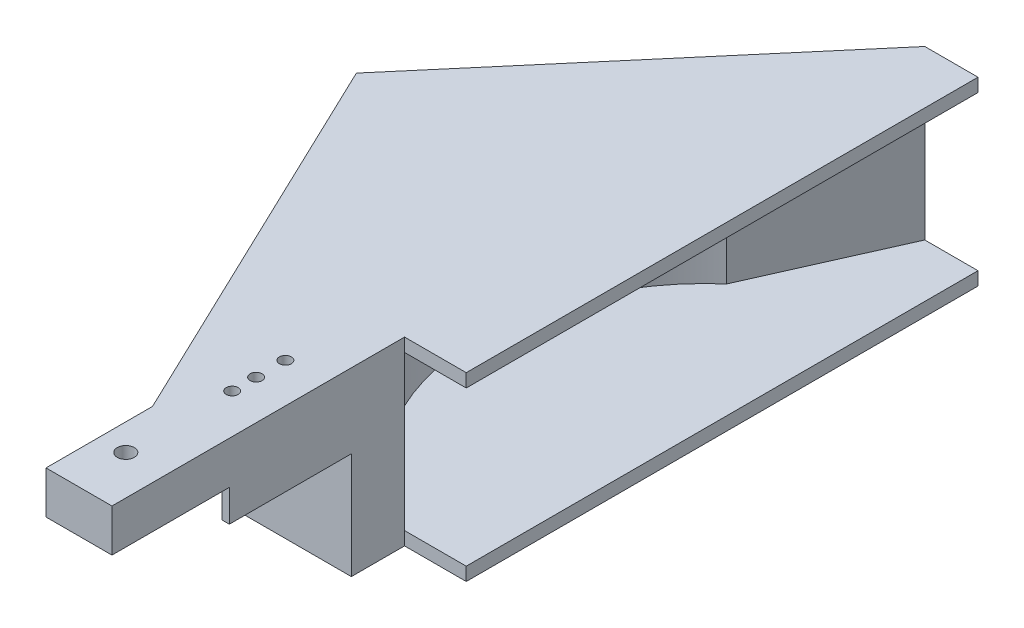
SolidWorks part; units mm, degrees
ref_plane "Front Plane" through (0, 0, 0) normal (0, 0, 1) x (1, 0, 0)
ref_plane "Top Plane" through (0, 0, 0) normal (0, 1, 0) x (1, 0, 0)
ref_plane "Right Plane" through (0, 0, 0) normal (1, 0, 0) x (0, 0, -1)
sketch "Sketch1" plane through (0, 0, 0) normal (0, 1, 0) x (1, 0, 0)
  line L0 (47.5, -78.4427) -> (47.5, -38.4427)
  line L1 (49.0919, 57.7552) -> (0, 0)
  line L2 (0, 0) -> (35.1, -73.4224)
  line L6 (35.1, -73.4224) -> (35.1, -93.4427)
  line L8 (37.5, -78.4427) -> (37.5, -93.4427) construction
  line L9 (37.5, -93.4427) -> (47.5, -93.4427)
  line L10 (47.5, -78.4427) -> (47.5, -93.4427)
  line L11 (35.1, -93.4427) -> (37.5, -93.4427)
  line L12 (35.1, -73.4224) -> (37.5, -78.4427) construction
  line L13 (49.0919, 57.7552) -> (37.628, 31.9779)
  arc A0 (37.628, 31.9779) -> (47.5, -38.4427) centre (65.622, 0) ccw
  point P6 (37.5, 31.9779)
  point P10 (47.5, 50)
  point P12 (49.0919, 57.7552)
  point P15 (51.2566, 50)
  point P16 (49.1521, 50)
  point P17 (50.3263, 51.8331)
  point P19 (0, 0)
  dimension "D1" = 85
  dimension "D10" = 114.085
  dimension "D2" = 50
  dimension "D3" = 40
  dimension "D4" = 47.5
  dimension "D5" = 10
  dimension "D8" = 15
  dimension "D9" = 12.4
extrude "Boss-Extrude1" add sketch "Sketch1" along normal blind 14
sketch "Sketch3" plane through (0, 0, 0) normal (0, -1, 0) x (1, 0, 0)
  line L6 (47.5, 93.4427) -> (47.5, 38.4427) construction
  line L7 (35.1, 93.4427) -> (47.5, 93.4427) construction
  line L8 (36.1851, 83.429) -> (36.1851, 109.2435) construction
  line L9 (33.255, 84.4031) -> (36.1851, 92.429)
  line L10 (35.3457, 53.1123) -> (33.255, 84.4031)
  line L11 (46.1351, 70.029) -> (44.8209, 53.0622)
  line L12 (46.1351, 88.029) -> (46.1351, 70.029)
  line L13 (44.8851, 92.429) -> (46.1351, 88.029)
  line L14 (36.1851, 92.429) -> (44.8851, 92.429)
  circle A6 centre (40.0851, 83.429) radius 6.75 construction
  circle A7 centre (40.0851, 83.429) radius 4.125
  circle A8 centre (40.0851, 63.429) radius 1.5 construction
  circle A9 centre (40.0851, 58.929) radius 1.5 construction
  circle A10 centre (40.0851, 53.429) radius 1.5 construction
  arc A11 (44.8209, 53.0622) -> (35.3457, 53.1123) centre (40.0851, 53.429) cw
  point P48 (33.3351, 83.429)
  dimension "D6" = 1.3649
  dimension "D7" = 2.6149
  dimension "D8" = 2.6791
  dimension "D12" = 1.0137
  dimension "D13" = 5.4137
  dimension "D1" = 3
  dimension "D3" = 8.25
  dimension "D4" = 13.5
  dimension "D5" = 4.75
  dimension "D2" = 40.0851
  dimension "D9" = 11.3149
  dimension "D10" = 12.1543
  dimension "D11" = 14.245
  dimension "D17" = 30.0137
  dimension "D18" = 34.5137
extrude "Cut-Extrude1" cut sketch "Sketch3" against normal blind 6
sketch "Sketch5" plane through (0, 6, 0) normal (0, -1, 0) x (1, 0, 0)
  circle A0 centre (40.0851, 63.429) radius 1.125
  circle A1 centre (40.0851, 58.929) radius 1.125
  circle A2 centre (40.0851, 53.429) radius 1.125
  circle A3 centre (40.0851, 63.429) radius 1.5 construction
  circle A4 centre (40.0851, 58.929) radius 1.5 construction
  circle A5 centre (40.0851, 53.429) radius 1.5 construction
  dimension "D1" = 2.25
extrude "Cut-Extrude2" cut sketch "Sketch5" against normal blind 15
sketch "Sketch15" plane through (0, 6, 0) normal (0, -1, 0) x (-1, 0, 0)
  line L1 (-32.171, -71.3827) -> (-57.8606, -71.3827)
  line L2 (-32.171, -71.3827) -> (-30.98, -110.0987)
  line L3 (-30.98, -110.0987) -> (-57.8606, -110.0987)
  line L4 (-57.8606, -71.3827) -> (-57.8606, -110.0987)
extrude "Cut-Extrude5" cut sketch "Sketch15" along normal up to surface (6 mm away) up to face at (37.1784, 0, 53.1275)
sketch "Sketch16" plane through (0, 14, 0) normal (0, 1, 0) x (1, 0, 0)
  circle A0 centre (40.0851, -83.429) radius 1.6
  circle A1 centre (40.0851, -63.429) radius 1.125 construction
  dimension "D1" = 20
  dimension "D2" = 3.2
extrude "Cut-Extrude6" cut sketch "Sketch16" against normal up to next
sketch "Sketch17" plane through (0, 0, 0) normal (0, -1, 0) x (-1, 0, 0)
  line L0 (-37.628, 31.9779) -> (-49.0919, 57.7552)
  line L1 (-49.0919, 57.7552) -> (0, 0)
  line L2 (-49.0919, 57.7552) -> (0, 0) construction
  line L4 (-47.5, -38.4427) -> (-47.5, -48.4427)
  line L5 (-47.5, -48.4427) -> (-23.1583, -48.4427)
  line L6 (-23.1583, -48.4427) -> (0, 0)
  line L8 (-47.5, -71.3827) -> (-47.5, -38.4427) construction
  arc A0 (-47.5, -38.4427) -> (-37.628, 31.9779) centre (-65.622, 0) ccw
  arc A1 (-47.5, -38.4427) -> (-37.628, 31.9779) centre (-65.622, 0) ccw construction
  point P10 (0, 0)
  point P14 (0, 0)
  point P16 (-6.1324, 7.2146)
  point P17 (-3.598, -4.2811)
  point P19 (0, 0)
  point P20 (-28.2496, -36.7785)
  point P21 (0, 0)
  point P24 (0, 0)
  point P25 (0, 0)
  dimension "D1" = 90
  dimension "D2" = 10
extrude "Boss-Extrude2" add sketch "Sketch17" along normal blind 20
sketch "Sketch18" plane through (0, 14, 0) normal (0, 1, 0) x (1, 0, 0)
  line L0 (23.122, 27.2024) -> (49.0919, 57.7552)
  line L1 (49.0919, 57.7552) -> (59.0919, 57.7552)
  line L2 (23.122, 27.2024) -> (23.122, -38.4427)
  line L3 (23.122, -38.4427) -> (59.0919, -38.4427)
  line L4 (59.0919, 57.7552) -> (59.0919, -38.4427)
  line L5 (49.0919, 57.7552) -> (0, 0) construction
  arc A0 (37.628, 31.9779) -> (47.5, -38.4427) centre (65.622, 0) ccw construction
  point P12 (57.4714, -38.4427)
  dimension "D1" = 10
extrude "Boss-Extrude3" add sketch "Sketch18" against normal blind 2.5
extrude "Boss-Extrude4" add sketch "Sketch18<2>" along normal blind 2.5 from surface starting at face at (30.9746, -20, 8.0438)
sketch "Sketch18<2>" plane through (0, 14, 0) normal (0, 1, 0) x (1, 0, 0) same geometry as "Sketch18"
equation "\"A\"= 20mm"
equation "\"B\"= 3"
equation "\"5.000000mmB\"=5"
